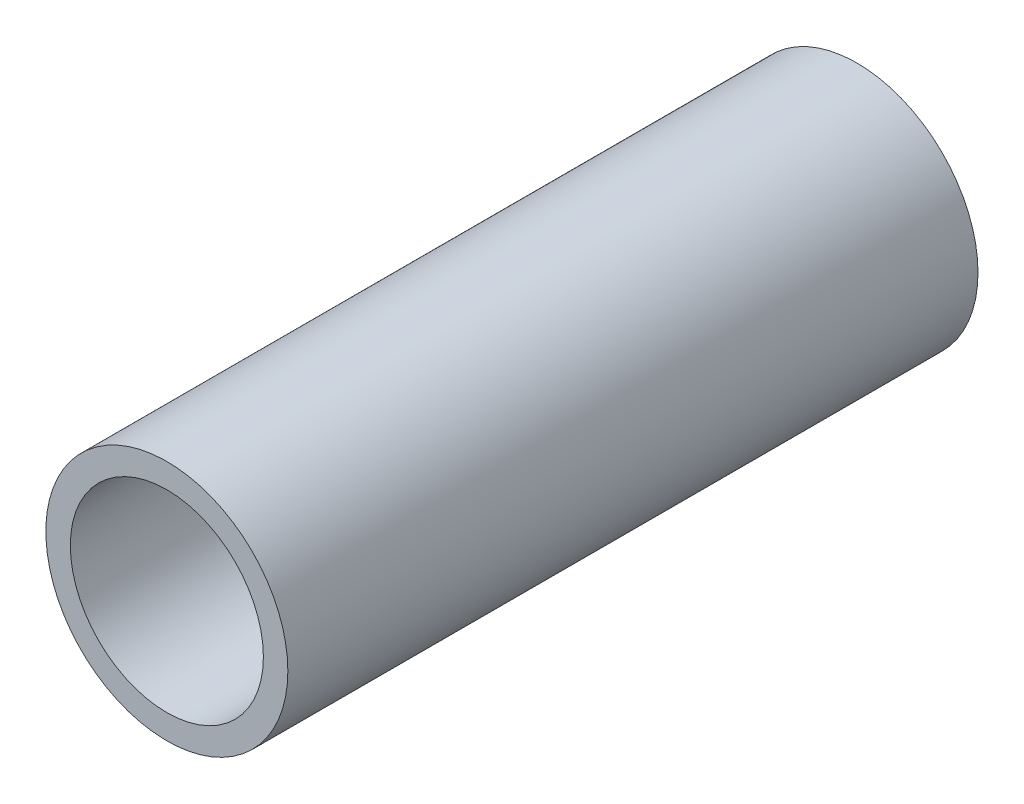
SolidWorks part; units mm, degrees
ref_plane "Front Plane" through (0, 0, 0) normal (0, 0, 1) x (1, 0, 0)
ref_plane "Top Plane" through (0, 0, 0) normal (0, 1, 0) x (1, 0, 0)
ref_plane "Right Plane" through (0, 0, 0) normal (1, 0, 0) x (0, 0, -1)
sketch "Sketch1" plane through (0, 0, 0) normal (0, 0, 1) x (1, 0, 0)
  circle A0 centre (0, 0) radius 16.7005
  dimension "Pipe OD" = 33.401
extrude "Extrude-Thin1" add sketch "Sketch1" along normal mid plane 95.25 thin thin type one direction reverse wall 3.3782
